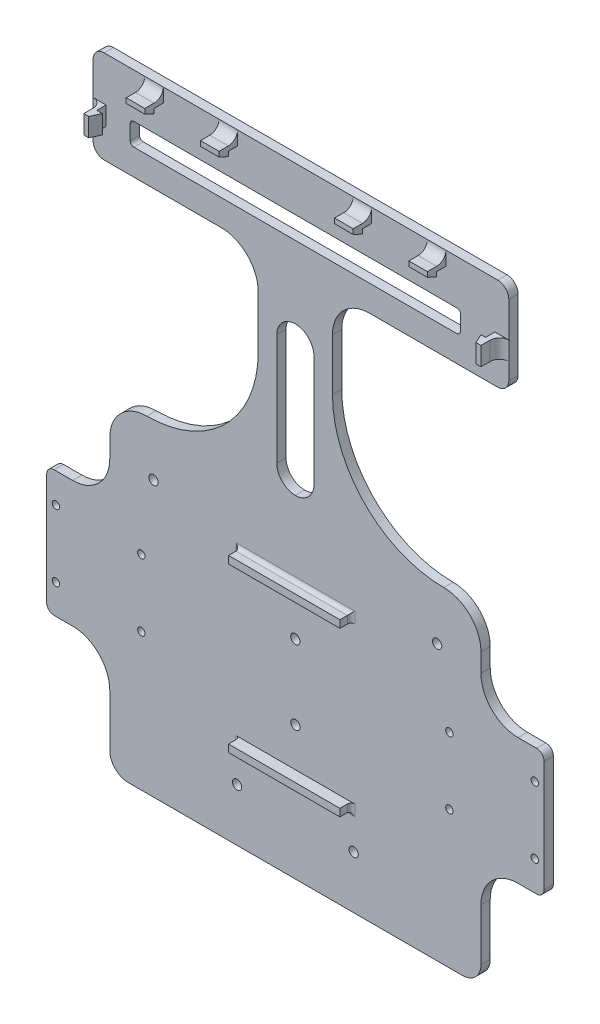
SolidWorks part; units mm, degrees
ref_plane "Alzado" through (0, 0, 0) normal (0, 0, 1) x (1, 0, 0)
ref_plane "Planta" through (0, 0, 0) normal (0, 1, 0) x (1, 0, 0)
ref_plane "Vista lateral" through (0, 0, 0) normal (1, 0, 0) x (0, 0, -1)
sketch "Croquis1" plane through (0, 0, 0) normal (0, 0, 1) x (1, 0, 0)
  line L0 (10, 65.5) -> (-10, 65.5)
  line L1 (67, -2.5) -> (67, -36.5)
  line L2 (-67, -2.5) -> (-67, -36.5)
  line L3 (50, -65.5) -> (-50, -65.5)
  line L6 (10, 22.5) -> (50, 22.5)
  line L7 (-50, -65.5) -> (50, -65.5)
  line L8 (-50, -65.5) -> (-50, -36.5)
  line L10 (50, -65.5) -> (50, -36.5)
  line L11 (-67, -36.5) -> (-50, -36.5)
  line L12 (-67, -36.5) -> (-67, -2.5)
  line L13 (-67, -2.5) -> (-50, -2.5)
  line L14 (67.1342, -36.5) -> (67.1342, -2.5)
  line L16 (-50, -2.5) -> (-50, 22.5)
  line L17 (-50, 22.5) -> (-10, 22.5)
  line L18 (50, -2.5) -> (50, 22.5)
  line L20 (-10, 22.5) -> (-10, 65.5)
  line L21 (-10, 65.5) -> (10, 65.5)
  line L22 (10, 22.5) -> (10, 65.5)
  line L23 (50, -2.5) -> (67.1342, -2.5)
  line L26 (50, -36.5) -> (67.1342, -36.5)
  point P1 (0, 0)
extrude "Saliente-Extruir1" add sketch "Croquis1" along normal blind 2.5 contours L10 L26 L1 L23 L18 L6 L22 L0 L20 L17 L16 L13 L2 L11 L8 L3 region at (0, -16.0782, 0)
fillet "Redondeo1" radius 10 6 edges at (-50, -2.5, 1.25) (-50, 22.5, 1.25) (50, 22.5, 1.25) (50, -2.5, 1.25) (-50, -36.5, 1.25) (50, -36.5, 1.25)
fillet "Redondeo2" radius 30 2 edges at (10, 22.5, 1.25) (-10, 22.5, 1.25)
fillet "Redondeo3" radius 5 2 edges at (-50, -65.5, 1.25) (50, -65.5, 1.25)
fillet "Redondeo4" radius 2 4 edges at (67, -2.5, 1.25) (67, -36.5, 1.25) (-67, -2.5, 1.25) (-67, -36.5, 1.25)
sketch "Croquis2" plane through (0, 0, 0) normal (0, 0, -1) x (-1, 0, 0)
  line L0 (-50, -60.5) -> (-50, -46.5) construction
  line L1 (-45, -65.5) -> (45, -65.5) construction
  circle A0 centre (-15.7, -51.32) radius 1.25
  dimension "D1" = 34.3
  dimension "D2" = 14.18
extrude "Cortar-Extruir1" cut sketch "Croquis2" against normal blind 2.5
mirror "Simetría1" about plane through (0, 0, 0) normal (1, 0, 0) of "Cortar-Extruir1"
sketch "Croquis3" plane through (0, 0, 2.5) normal (0, 0, 1) x (1, 0, 0)
  line L0 (45, -65.5) -> (-45, -65.5) construction
  line L1 (-15, -40) -> (15, -40)
  line L2 (-15, -40) -> (-15, -42)
  line L3 (-15, -42) -> (15, -42)
  line L4 (15, -40) -> (15, -42)
  dimension "D1" = 23.5
extrude "Saliente-Extruir2" add sketch "Croquis3" along normal blind 3
sketch "Croquis4" plane through (0, 0, 2.5) normal (0, 0, 1) x (1, 0, 0)
  circle A0 centre (64.5, -28.5) radius 1
  circle A1 centre (64.5, -10.5) radius 1
  circle A2 centre (41.5, -28.5) radius 1
  circle A3 centre (41.5, -10.5) radius 1
  circle A4 centre (0, -9.5) radius 1.25
  circle A5 centre (0, -29.5) radius 1.25
extrude "Cortar-Extruir2" cut sketch "Croquis4" against normal blind 2.5
mirror "Simetría2" about plane through (0, 0, 0) normal (1, 0, 0) of "Cortar-Extruir2"
sketch "Croquis5" plane through (0, 0, 2.5) normal (0, 0, 1) x (1, 0, 0)
  circle A0 centre (38.2, 8.5) radius 1.25
extrude "Cortar-Extruir3" cut sketch "Croquis5" against normal blind 2.5
mirror "Simetría3" about plane through (0, 0, 0) normal (1, 0, 0) of "Cortar-Extruir3"
sketch "Croquis6" plane through (0, 0, 2.5) normal (0, 0, 1) x (1, 0, 0)
  line L0 (15, -40) -> (-15, -40) construction
  line L1 (-15, 4) -> (15, 4)
  line L2 (-15, 4) -> (-15, 2)
  line L3 (-15, 2) -> (15, 2)
  line L4 (15, 4) -> (15, 2)
  dimension "D1" = 42
extrude "Saliente-Extruir3" add sketch "Croquis6" along normal blind 3
fillet "Redondeo5" radius 1 6 edges at (-15, -41, 2.5) (15, -41, 2.5) (0, -42, 2.5) (-15, 3, 2.5) (15, 3, 2.5) (0, 4, 2.5)
sketch "Croquis7" plane through (0, 0, 2.5) normal (0, 0, 1) x (1, 0, 0)
  line L1 (-54.5, 101.5) -> (57.5, 101.5)
  line L2 (-54.5, 101.5) -> (-54.5, 76.5)
  line L3 (-10, 65.5) -> (10, 65.5)
  line L4 (57.5, 101.5) -> (57.5, 76.5)
  line L7 (-10, 65.5) -> (-10, 76.5)
  line L8 (10, 65.5) -> (10, 76.5)
  line L9 (-10, 76.5) -> (-54.5, 76.5)
  line L10 (10, 76.5) -> (57.5, 76.5)
  line L24 (67, -34.5) -> (67, -4.5)
  line L25 (65, -2.5) -> (60, -2.5)
  line L26 (50, 7.5) -> (50, 12.5)
  line L27 (10, 52.5) -> (10, 65.5)
  line L28 (10, 65.5) -> (-10, 65.5)
  line L29 (-10, 65.5) -> (-10, 52.5)
  line L30 (-50, 12.5) -> (-50, 7.5)
  line L31 (-60, -2.5) -> (-65, -2.5)
  line L32 (-67, -4.5) -> (-67, -34.5)
  line L33 (-65, -36.5) -> (-60, -36.5)
  line L34 (-50, -46.5) -> (-50, -60.5)
  line L35 (-45, -65.5) -> (45, -65.5)
  line L36 (50, -60.5) -> (50, -46.5)
  line L37 (60, -36.5) -> (65, -36.5)
  line L38 (67, -34.5) -> (67, -4.5)
  line L39 (65, -2.5) -> (60, -2.5)
  line L40 (50, 7.5) -> (50, 12.5)
  line L41 (10, 52.5) -> (10, 65.5)
  line L43 (-10, 65.5) -> (-10, 52.5)
  line L44 (-50, 12.5) -> (-50, 7.5)
  line L45 (-60, -2.5) -> (-65, -2.5)
  line L46 (-67, -4.5) -> (-67, -34.5)
  line L47 (-65, -36.5) -> (-60, -36.5)
  line L48 (-50, -46.5) -> (-50, -60.5)
  line L49 (-45, -65.5) -> (45, -65.5)
  line L50 (50, -60.5) -> (50, -46.5)
  line L51 (60, -36.5) -> (65, -36.5)
  arc A14 (67, -4.5) -> (65, -2.5) centre (65, -4.5) ccw
  arc A15 (50, 7.5) -> (60, -2.5) centre (60, 7.5) ccw
  arc A16 (50, 12.5) -> (40, 22.5) centre (40, 12.5) ccw
  arc A17 (10, 52.5) -> (40, 22.5) centre (40, 52.5) ccw
  arc A18 (-40, 22.5) -> (-10, 52.5) centre (-40, 52.5) ccw
  arc A19 (-40, 22.5) -> (-50, 12.5) centre (-40, 12.5) ccw
  arc A20 (-60, -2.5) -> (-50, 7.5) centre (-60, 7.5) ccw
  arc A21 (-65, -2.5) -> (-67, -4.5) centre (-65, -4.5) ccw
  arc A22 (-67, -34.5) -> (-65, -36.5) centre (-65, -34.5) ccw
  arc A23 (-50, -46.5) -> (-60, -36.5) centre (-60, -46.5) ccw
  arc A24 (-50, -60.5) -> (-45, -65.5) centre (-45, -60.5) ccw
  arc A25 (45, -65.5) -> (50, -60.5) centre (45, -60.5) ccw
  arc A26 (60, -36.5) -> (50, -46.5) centre (60, -46.5) ccw
  arc A27 (65, -36.5) -> (67, -34.5) centre (65, -34.5) ccw
  arc A28 (67, -4.5) -> (65, -2.5) centre (65, -4.5) ccw
  arc A29 (50, 7.5) -> (60, -2.5) centre (60, 7.5) ccw
  arc A30 (50, 12.5) -> (40, 22.5) centre (40, 12.5) ccw
  arc A31 (10, 52.5) -> (40, 22.5) centre (40, 52.5) ccw
  arc A32 (-40, 22.5) -> (-10, 52.5) centre (-40, 52.5) ccw
  arc A33 (-40, 22.5) -> (-50, 12.5) centre (-40, 12.5) ccw
  arc A34 (-60, -2.5) -> (-50, 7.5) centre (-60, 7.5) ccw
  arc A35 (-65, -2.5) -> (-67, -4.5) centre (-65, -4.5) ccw
  arc A36 (-67, -34.5) -> (-65, -36.5) centre (-65, -34.5) ccw
  arc A37 (-50, -46.5) -> (-60, -36.5) centre (-60, -46.5) ccw
  arc A38 (-50, -60.5) -> (-45, -65.5) centre (-45, -60.5) ccw
  arc A39 (45, -65.5) -> (50, -60.5) centre (45, -60.5) ccw
  arc A40 (60, -36.5) -> (50, -46.5) centre (60, -46.5) ccw
  arc A41 (65, -36.5) -> (67, -34.5) centre (65, -34.5) ccw
  dimension "D1" = 0
  dimension "D2" = 44.5
  dimension "D3" = 47.5
extrude "Saliente-Extruir6" add sketch "Croquis7" against normal blind 2.5 contours L8 L10 L4 L1 L2 L9 L7 L3 region at (1.3907, 87.6887, 2.5)
fillet "Redondeo7" radius 10 2 edges at (-10, 76.5, 1.25) (10, 76.5, 1.25)
fillet "Redondeo8" radius 3 4 edges at (-54.5, 101.5, 1.25) (57.5, 101.5, 1.25) (57.5, 76.5, 1.25) (-54.5, 76.5, 1.25)
sketch "Croquis8" plane through (0, 0, 2.5) normal (0, 0, 1) x (1, 0, 0)
  line L1 (-44.5, 89.5) -> (44.5, 89.5)
  line L2 (-44.5, 89.5) -> (-44.5, 83.5)
  line L3 (-44.5, 83.5) -> (44.5, 83.5)
  line L4 (44.5, 89.5) -> (44.5, 83.5)
  line L10 (-10, 52.5) -> (-10, 66.5) construction
  dimension "D1" = 34.5
extrude "Cortar-Extruir5" cut sketch "Croquis8" against normal blind 2.5
fillet "Redondeo10" radius 1 4 edges at (44.5, 89.5, 1.25) (44.5, 83.5, 1.25) (-44.5, 83.5, 1.25) (-44.5, 89.5, 1.25)
sketch "Croquis9" plane through (0, 0, 2.5) normal (0, 0, 1) x (1, 0, 0)
  line L1 (-52, 89.5945) -> (-49.5, 89.5945)
  line L2 (-52, 89.5945) -> (-52, 84.5945)
  line L3 (-52, 84.5945) -> (-49.5, 84.5945)
  line L4 (-49.5, 89.5945) -> (-49.5, 84.5945)
extrude "Saliente-Extruir7" add sketch "Croquis9" along normal blind 5
fillet "Redondeo11" radius 2.5 1 edges at (-52, 87.0945, 2.5)
sketch "Croquis10" plane through (0, 0, 2.5) normal (0, 0, 1) x (1, 0, 0)
  line L1 (-49.5, 84.5945) -> (-51, 84.5945)
  line L2 (-49.5, 84.5945) -> (-49.5, 89.5945)
  line L3 (-49.5, 89.5945) -> (-51, 89.5945)
  line L4 (-51, 84.5945) -> (-51, 89.5945)
extrude "Cortar-Extruir6" cut sketch "Croquis10" along normal blind 2.5
chamfer "Chaflán1" distance 2.5 angle 25 1 edges at (-49.5, 87.0945, 7.5) first distance on face at (-49.5, 87.0945, 6.25)
sketch "Croquis11" plane through (0, 0, 2.5) normal (0, 0, 1) x (1, 0, 0)
  line L1 (52.5, 89) -> (55, 89)
  line L2 (52.5, 89) -> (52.5, 84)
  line L3 (52.5, 84) -> (55, 84)
  line L4 (55, 89) -> (55, 84)
extrude "Saliente-Extruir8" add sketch "Croquis11" along normal blind 5
sketch "Croquis12" plane through (0, 0, 2.5) normal (0, 0, 1) x (1, 0, 0)
  line L0 (55, 89) -> (52.5, 89) construction
  line L1 (52.5, 84) -> (53.75, 84)
  line L2 (52.5, 84) -> (52.5, 89)
  line L3 (52.5, 89) -> (53.75, 89)
  line L4 (53.75, 84) -> (53.75, 89)
extrude "Cortar-Extruir7" cut sketch "Croquis12" along normal blind 2.5
chamfer "Chaflán2" distance 2.5 angle 25 1 edges at (52.5, 86.5, 7.5) first distance on face at (52.5, 86.5, 6.25)
fillet "Redondeo13" radius 2.5 1 edges at (55, 86.5, 2.5)
sketch "Croquis13" plane through (0, 0, 2.5) normal (0, 0, 1) x (1, 0, 0)
  line L1 (-40.567, 99) -> (-35.567, 99)
  line L2 (-40.567, 99) -> (-40.567, 96.5)
  line L3 (-40.567, 96.5) -> (-35.567, 96.5)
  line L4 (-35.567, 99) -> (-35.567, 96.5)
  line L6 (-20.567, 99) -> (-15.567, 99)
  line L7 (-20.567, 99) -> (-20.567, 96.5)
  line L8 (-20.567, 96.5) -> (-15.567, 96.5)
  line L9 (-15.567, 99) -> (-15.567, 96.5)
extrude "Saliente-Extruir9" add sketch "Croquis13" along normal blind 5
fillet "Redondeo14" radius 2.5 2 edges at (-18.067, 99, 2.5) (-38.067, 99, 2.5)
sketch "Croquis14" plane through (0, 0, 2.5) normal (0, 0, 1) x (1, 0, 0)
  line L0 (-35.567, 96.5) -> (-35.567, 99) construction
  line L1 (-40.567, 96.5) -> (-35.567, 96.5)
  line L2 (-40.567, 96.5) -> (-40.567, 97.75)
  line L3 (-40.567, 97.75) -> (-35.567, 97.75)
  line L4 (-35.567, 96.5) -> (-35.567, 97.75)
  line L5 (-15.567, 96.5) -> (-15.567, 99) construction
  line L6 (-20.567, 96.5) -> (-15.567, 96.5)
  line L7 (-20.567, 96.5) -> (-20.567, 97.75)
  line L8 (-20.567, 97.75) -> (-15.567, 97.75)
  line L9 (-15.567, 96.5) -> (-15.567, 97.75)
extrude "Cortar-Extruir8" cut sketch "Croquis14" along normal blind 2.5
chamfer "Chaflán3" distance 2.5 angle 25 2 edges at (-18.067, 96.5, 7.5) (-38.067, 96.5, 7.5) first distance on face at (-18.067, 96.5, 6.25) first distance on face at (-38.067, 96.5, 6.25)
mirror "Simetría4" about plane through (0, 0, 0) normal (1, 0, 0) of "Chaflán3", "Cortar-Extruir8", "Redondeo14", "Saliente-Extruir9"
sketch "Croquis17" plane through (0, 0, 2.5) normal (0, 0, 1) x (1, 0, 0)
  line L1 (-5, 64) -> (5, 64)
  line L2 (-5, 64) -> (-5, 24)
  line L3 (-5, 24) -> (5, 24)
  line L4 (5, 64) -> (5, 24)
extrude "Cortar-Extruir9" cut sketch "Croquis17" against normal blind 2.5
fillet "Redondeo19" radius 5 4 edges at (-5, 24, 1.25) (5, 24, 1.25) (5, 64, 1.25) (-5, 64, 1.25)
